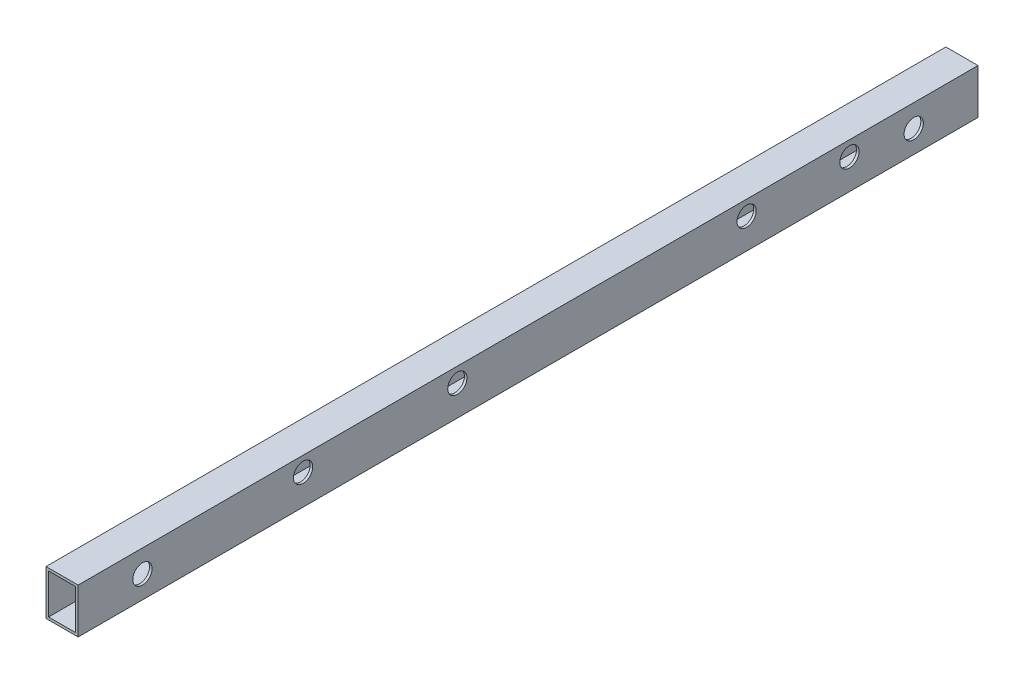
SolidWorks part; units mm, degrees
ref_plane "Front Plane" through (0, 0, 0) normal (0, 0, 1) x (1, 0, 0)
ref_plane "Top Plane" through (0, 0, 0) normal (0, 1, 0) x (1, 0, 0)
ref_plane "Right Plane" through (0, 0, 0) normal (1, 0, 0) x (0, 0, -1)
sketch "Sketch1" plane through (0, 0, 0) normal (0, 0, 1) x (1, 0, 0)
  line L1 (0, 0) -> (50, 0)
  line L2 (0, 0) -> (0, -70)
  line L3 (0, -70) -> (50, -70)
  line L4 (50, 0) -> (50, -70)
  line L5 (4, -4) -> (46, -4)
  line L6 (4, -4) -> (4, -66)
  line L7 (4, -66) -> (46, -66)
  line L8 (46, -4) -> (46, -66)
  dimension "D1" = 70
  dimension "D2" = 50
  dimension "D3" = 4
  dimension "D4" = 4
  dimension "D5" = 4
  dimension "D6" = 4
extrude "Boss-Extrude2" add sketch "Sketch1" along normal blind 1400
sketch "Sketch2" plane through (50, 0, 0) normal (1, 0, 0) x (0, 0, -1)
  line L0 (-1400, -70) -> (-1400, 0) construction
  line L1 (-1400, 0) -> (0, 0) construction
  circle A0 centre (-1050, -23) radius 15
  circle A1 centre (-200, -23) radius 15
  circle A2 centre (-810, -23) radius 15
  circle A3 centre (-360, -23) radius 15
  dimension "D1" = 30
  dimension "D2" = 30
  dimension "D3" = 30
  dimension "D4" = 30
  dimension "D5" = 350
  dimension "D6" = 240
  dimension "D7" = 450
  dimension "D8" = 160
  dimension "D9" = 23
extrude "Cut-Extrude1" cut sketch "Sketch2" against normal through all
sketch "Sketch3" plane through (50, 0, 0) normal (1, 0, 0) x (0, 0, -1)
  line L0 (-1400, -70) -> (-1400, 0) construction
  line L2 (-1400, 0) -> (0, 0) construction
  line L3 (0, -70) -> (0, 0) construction
  circle A0 centre (-1300, -35) radius 15
  circle A1 centre (-100, -35) radius 15
  point P7 (0, 0)
  dimension "D1" = 30
  dimension "D4" = 30
  dimension "D2" = 100
  dimension "D3" = 35
  dimension "D5" = 100
extrude "Cut-Extrude2" cut sketch "Sketch3" against normal through all
equation "\"D4@Sketch1\"=\"D3@Sketch1\""
equation "\"D5@Sketch1\"=\"D3@Sketch1\""
equation "\"D2@Sketch2\"=\"D1@Sketch2\""
